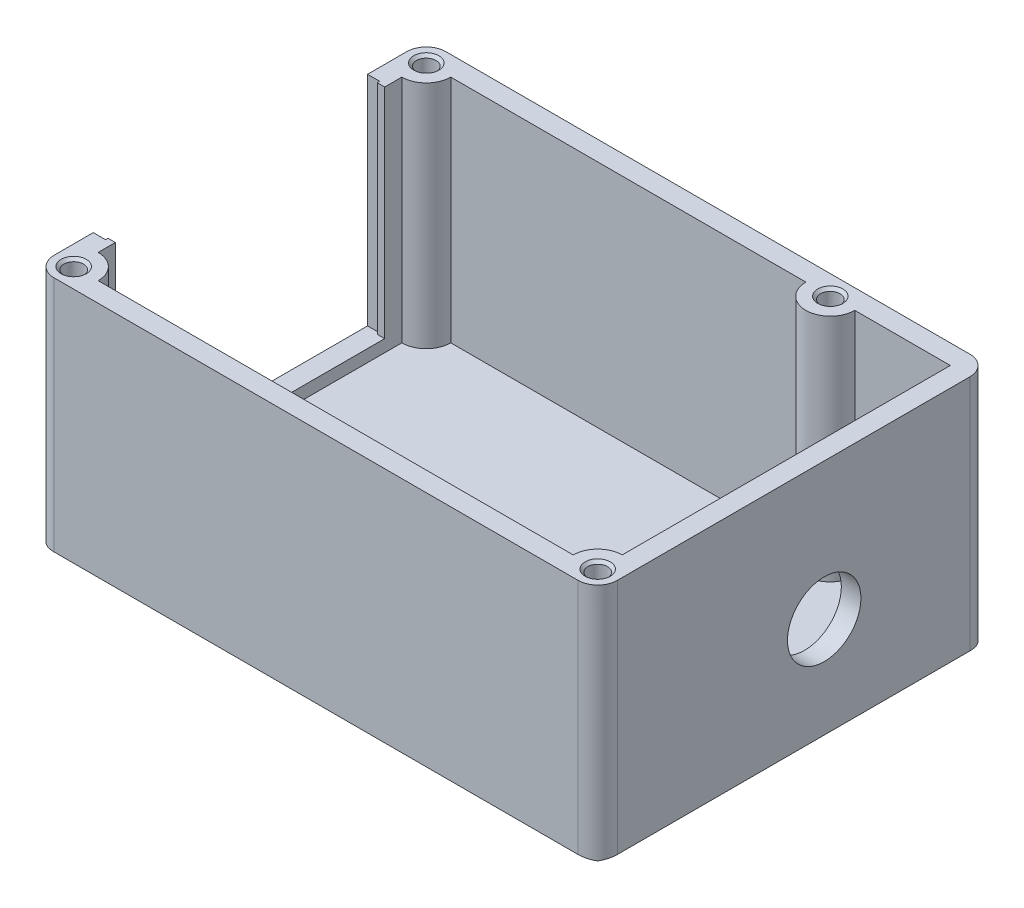
SolidWorks part; units mm, degrees
material "201.0-T7 Insulated Mold Casting (SS)"
ref_plane "Front Plane" through (0, 0, 0) normal (0, 0, 1) x (1, 0, 0)
ref_plane "Top Plane" through (0, 0, 0) normal (0, 1, 0) x (1, 0, 0)
ref_plane "Right Plane" through (0, 0, 0) normal (1, 0, 0) x (0, 0, -1)
sketch "Sketch1" plane through (0, 0, 0) normal (0, 1, 0) x (1, 0, 0)
  line L0 (0, 0) -> (-14, 0) construction
  line L1 (-14, 16) -> (32, 16)
  line L2 (-14, 16) -> (-14, -16)
  line L3 (-14, -16) -> (32, -16)
  line L4 (32, 16) -> (32, -16)
  dimension "D1" = 32
  dimension "D2" = 46
  dimension "D3" = 14
extrude "Boss-Extrude1" add sketch "Sketch1" against normal blind 20.6
hole_wizard "M2x0.4 Tapped Hole1" positions "Sketch3" profile "Sketch2" tap size "M2x0.4" standard "ANSI Metric"
sketch "Sketch3" plane through (0, 0, 0) normal (0, 1, 0) x (1, 0, 0)
  line L0 (-12.4, 14.4) -> (20.6, 14.4) construction
  line L2 (30.4, -14.4) -> (-12.4, -14.4) construction
  line L4 (-14, 16) -> (-14, -16) construction
  line L5 (32, 16) -> (-14, 16) construction
  line L8 (-14, -16) -> (32, -16) construction
  line L9 (32, -16) -> (32, 16) construction
  line L10 (-12.4, 14.4) -> (-12.4, -14.4) construction
  point P0 (-12.4, 14.4)
  point P2 (20.6, 14.4)
  point P4 (30.4, -14.4)
  point P6 (-12.4, -14.4)
  dimension "D1" = 1.6
  dimension "D2" = 1.6
  dimension "D3" = 1.6
  dimension "D4" = 1.6
  dimension "D5" = 33
sketch "Sketch2" plane through (-12.4, 0, -14.4) normal (1, 0, 0) x (0, 0, 1)
  line L0 (0, 0) -> (0, 6.4807)
  line L1 (0, 6.4807) -> (0.8, 6)
  line L2 (0.8, 6) -> (0.8, 0.225)
  line L3 (0.8, 0.225) -> (1.025, 0)
  line L5 (1.025, 0) -> (0, 0)
  line L6 (-0.8, 0.225) -> (-1.025, 0) construction
  line L10 (0, 6.4807) -> (-0.8, 6) construction
  line L11 (0, -6.35) -> (0, 107.95) construction
  dimension "Tap Drill Dia." = 1.6
  dimension "Tap Drill Depth" = 6
  dimension "Near C'Sink Dia." = 2.05
  dimension "Near C'Sink Angle" = 90
  dimension "Drill Angle" = 118
sketch "Sketch4" plane through (0, -20.6, 0) normal (0, -1, 0) x (-1, 0, 0)
  line L0 (-11, -5.5) -> (-11, 5.5) construction
  line L1 (0, 0) -> (-11, 0) construction
  circle A0 centre (0, 0) radius 6
  dimension "D1" = 12
  dimension "D2" = 11
  dimension "D3" = 11
fillet "Fillet1" radius 1.6 4 edges at (-14, -10.3, -16) (32, -10.3, -16) (32, -10.3, 16) (-14, -10.3, 16)
extrude "Boss-Extrude2" add sketch "Sketch4" along normal blind 0.5
sketch "Sketch8" plane through (0, 0, 0) normal (0, 1, 0) x (1, 0, 0)
  line L0 (30.4, 16) -> (-12.4, 16) construction
  line L1 (-10.4, 14.4) -> (18.6, 14.4)
  line L2 (-12.4, 12.4) -> (-12.4, -12.4)
  line L3 (-10.4, -14.4) -> (28.4, -14.4)
  line L4 (30.4, 14.4) -> (30.4, -12.4)
  line L5 (-12.4, 14.4) -> (30.4, -14.4) construction
  line L6 (-12.4, -14.4) -> (30.4, 14.4) construction
  line L7 (-12.4, -16) -> (30.4, -16) construction
  line L8 (32, -14.4) -> (32, 14.4) construction
  line L9 (-14, 14.4) -> (-14, -14.4) construction
  line L10 (22.6, 14.4) -> (30.4, 14.4)
  arc A0 (-12.4, 12.4) -> (-10.4, 14.4) centre (-12.4, 14.4) ccw
  arc A1 (18.6, 14.4) -> (22.6, 14.4) centre (20.6, 14.4) ccw
  arc A2 (30.4, -12.4) -> (28.4, -14.4) centre (30.4, -14.4) ccw
  arc A3 (-10.4, -14.4) -> (-12.4, -12.4) centre (-12.4, -14.4) ccw
  circle A4 centre (-12.4, 14.4) radius 0.8 construction
  circle A5 centre (30.4, -14.4) radius 0.8 construction
  circle A6 centre (-12.4, -14.4) radius 0.8 construction
  point P0 (9, 0)
  dimension "D5" = 4
  dimension "D1" = 1.6
  dimension "D2" = 1.6
  dimension "D3" = 1.6
  dimension "D4" = 1.6
extrude "Cut-Extrude3" cut sketch "Sketch8" against normal offset from surface (18.8 mm away) 1.8 up to face at (0, -20.6, 6)
sketch "Sketch6" plane through (0, 0, 0) normal (0, 1, 0) x (1, 0, 0)
  line L0 (-14, 14.4) -> (-14, -14.4) construction
  line L1 (-12, 11) -> (-14, 11)
  line L2 (-12, 11) -> (-12, -11)
  line L3 (-12, -11) -> (-14, -11)
  line L4 (-14, 11) -> (-14, -11)
  line L5 (-12, 11) -> (-14, -11) construction
  line L6 (-12, -11) -> (-14, 11) construction
  line L7 (0, 0) -> (-13, 0) construction
  point P0 (-13, 0)
  dimension "D1" = 2
  dimension "D2" = 22
extrude "Cut-Extrude1" cut sketch "Sketch6" against normal offset from surface (17.8 mm away) 2.8 up to face at (0, -20.6, 6)
sketch "Sketch7" plane through (0, 0, 0) normal (0, 1, 0) x (1, 0, 0)
  line L0 (-14, -11) -> (-14, -14.4) construction
  line L1 (-13, 11.2) -> (-14, 11.2)
  line L2 (-13, 11.2) -> (-13, -11.2)
  line L3 (-13, -11.2) -> (-14, -11.2)
  line L4 (-14, 11.2) -> (-14, -11.2)
  line L5 (-13, 11.2) -> (-14, -11.2) construction
  line L6 (-13, -11.2) -> (-14, 11.2) construction
  line L7 (0, 0) -> (-13.5, 0) construction
  point P0 (-13.5, 0)
  dimension "D1" = 22.4
  dimension "D2" = 1
extrude "Cut-Extrude2" cut sketch "Sketch7" against normal up to surface (17.8 mm away) up to face at (-13.2, -17.8, 0)
sketch "Sketch9" plane through (32, 0, 0) normal (1, 0, 0) x (0, 0, -1)
  line L0 (-14.4, 0) -> (14.4, 0) construction
  line L1 (16, 0) -> (16, -20.6) construction
  circle A0 centre (2.5, -11.2) radius 3
  dimension "D2" = 6
  dimension "D3" = 13.5
  dimension "D1" = 11.2
extrude "Cut-Extrude4" cut sketch "Sketch9" against normal through all
chamfer "Chamfer1" distance 4.5 angle 15 4 edges at (9, -20.6, 16) (-14, -20.6, 0) (9, -20.6, -16) (32, -20.6, 0) first distance on face at (0, -20.6, 6)
